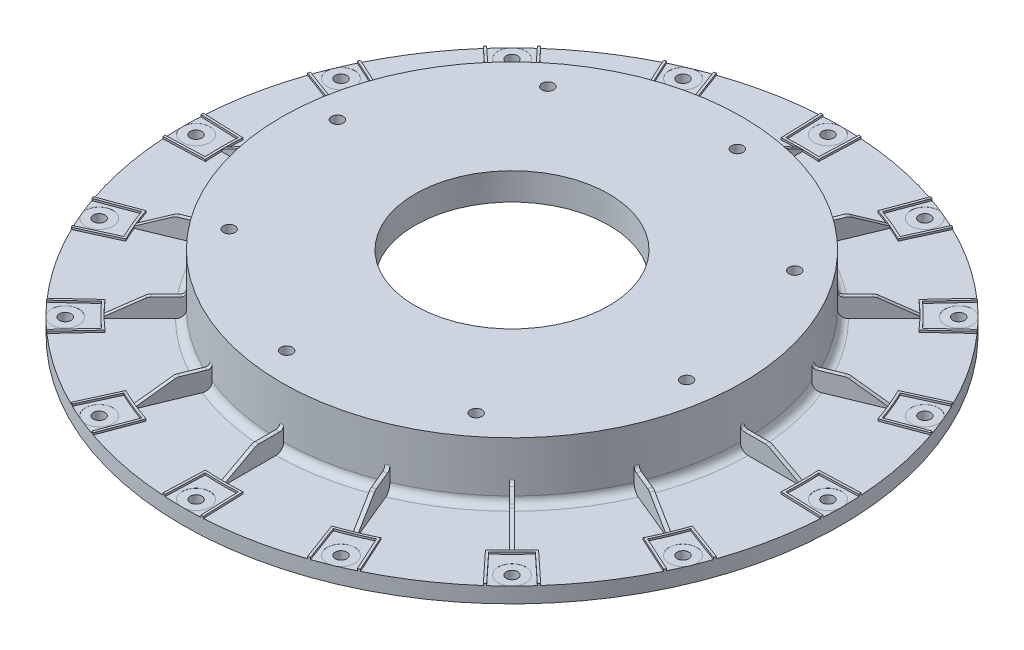
SolidWorks part; units mm, degrees
material "PF"
ref_plane "前视基准面" through (0, 0, 0) normal (0, 0, 1) x (1, 0, 0)
ref_plane "上视基准面" through (0, 0, 0) normal (0, 1, 0) x (1, 0, 0)
ref_plane "右视基准面" through (0, 0, 0) normal (1, 0, 0) x (0, 0, -1)
sketch "草图1" plane through (0, 0, 0) normal (0, 1, 0) x (1, 0, 0)
  circle A0 centre (0, 0) radius 85
  dimension "D1" = 170
extrude "凸台-拉伸1" add sketch "草图1" along normal blind 5
sketch "草图2" plane through (0, 5, 0) normal (0, 1, 0) x (1, 0, 0)
  circle A0 centre (0, 0) radius 81.5 construction
  circle A1 centre (0, 0) radius 85 construction
  circle A2 centre (-81.5, 0) radius 1.5
  dimension "D1" = 3.5
  dimension "D2" = 3
extrude "切除-拉伸1" cut sketch "草图2" against normal blind 50
pattern_circular "阵列(圆周)1" count 16 over 360 about axis through (0, 5, 0) along (0, 1, 0) of "切除-拉伸1"
sketch "草图3" plane through (0, 5, 0) normal (0, 1, 0) x (1, 0, 0)
  circle A0 centre (-75.2962, -31.1887) radius 3.55
  dimension "D1" = 7.1
extrude "切除-拉伸3" cut sketch "草图3" against normal blind 0.02
pattern_circular "阵列(圆周)2" count 16 over 360 about axis through (0, 5, 0) along (0, -1, 0) of "切除-拉伸3" reverse direction yes
sketch "草图4" plane through (0, 5, 0) normal (0, 1, 0) x (1, 0, 0)
  line L0 (-74.8787, 4.2634) -> (-84.8741, 4.625)
  line L1 (-74.8787, -4.2634) -> (-84.8741, -4.625)
  line L2 (-84.8393, 5.2242) -> (-74.2424, 4.8407)
  line L3 (-108.4611, 0) -> (191.6267, 0) construction
  line L4 (-84.8393, -5.2242) -> (-74.2424, -4.8407)
  arc A0 (-74.8787, 4.2634) -> (-74.8787, -4.2634) centre (0, 0) ccw
  arc A1 (-78.7598, 31.9671) -> (-84.9978, 0.6063) centre (0, 0) ccw construction
  arc A2 (-84.9978, -0.6063) -> (-78.7598, -31.9671) centre (0, 0) ccw construction
  arc A3 (-84.8393, 5.2242) -> (-84.8741, 4.625) centre (0, 0) ccw
  arc A4 (-74.2424, 4.8407) -> (-74.2424, -4.8407) centre (0, 0) ccw
  arc A5 (-84.8741, -4.625) -> (-84.8393, -5.2242) centre (0, 0) ccw
  point P11 (-81.5, 0)
  dimension "D1" = 10
  dimension "D5" = 0.6
  dimension "D2" = 4.5
  dimension "D3" = 4.5
  dimension "D4" = 0.6
  dimension "D6" = 0.6
extrude "凸台-拉伸2" add sketch "草图4" along normal blind 0.5
pattern_circular "阵列(圆周)3" count 16 over 360 about axis through (0, 5, 0) along (0, -1, 0) of "凸台-拉伸2" reverse direction yes
sketch "草图5" plane through (0, 0, 0) normal (0, 0, 1) x (1, 0, 0)
  line L0 (-74.4, 5.5) -> (-69.9462, 7.74)
  line L1 (-69.9462, 7.74) -> (-60.4731, 7.74)
sketch "草图6" plane through (0, 5, 0) normal (0, 1, 0) x (1, 0, 0)
  circle A0 centre (0, 0) radius 59.4
  arc A1 (-74.2424, 4.8407) -> (-74.2424, -4.8407) centre (0, 0) ccw construction
  dimension "D1" = 15
extrude "凸台-拉伸3" add sketch "草图6" along normal blind 20
sketch "草图7" plane through (0, 25, 0) normal (0, 1, 0) x (1, 0, 0)
  circle A0 centre (0, 0) radius 54.4
  circle A1 centre (0, 0) radius 59.4 construction
  dimension "D1" = 5
extrude "切除-拉伸4" cut sketch "草图7" against normal blind 50
sketch "草图8" plane through (0, 0, 0) normal (0, 0, 1) x (1, 0, 0)
  line L0 (-74.4, 5.5) -> (-66.3389, 9.8206)
  line L1 (-66.3389, 9.8206) -> (-59.4, 9.8206)
  line L2 (-59.4, 25) -> (-59.4, 5) construction
  line L5 (-56.2964, 5) -> (-49.0744, 5) construction
  line L6 (-57.9, 5) -> (-74.3212, 5)
  line L7 (-74.2424, 5) -> (-74.4, 5) construction
  line L9 (-59.4, 9.8206) -> (-57.9, 9.8206)
  line L10 (-57.9, 9.8206) -> (-57.9, 5)
  line L12 (-74.4, 5.5) -> (-74.6578, 5.5)
  line L13 (-76.3821, 5.5) -> (-66.7385, 5.5) construction
  line L14 (-74.6578, 5.5) -> (-74.6578, 5)
  line L15 (-63.6845, 5) -> (-76.3821, 5) construction
  line L16 (-74.6578, 5) -> (-74.3212, 5)
  dimension "D1" = 1.5
sketch "草图9" plane through (0, 25, 0) normal (0, 1, 0) x (1, 0, 0)
  circle A0 centre (0, 0) radius 56.4
  circle A1 centre (0, 0) radius 54.4 construction
  dimension "D1" = 2
extrude "切除-拉伸5" cut sketch "草图9" against normal blind 500
sketch "草图10" plane through (0, 25, 0) normal (0, 1, 0) x (1, 0, 0)
  circle A0 centre (0, 0) radius 58.5201
  circle A1 centre (0, 0) radius 25
  dimension "D1" = 50
extrude "凸台-拉伸5" add sketch "草图10" against normal blind 2
fillet "圆角3" radius 2 1 edges at (0, 5, 59.4)
extrude "凸台-拉伸6" add sketch "草图8" along normal mid plane 1
pattern_circular "阵列(圆周)5" count 16 over 360 about axis through (0, 5, 0) along (0, -1, 0) of "凸台-拉伸6" reverse direction yes
fillet "圆角11" radius 2 1 edges at (-66.3389, 9.8206, 0)
fillet "圆角14" radius 1 1 edges at (-59.4, 9.8206, 0)
fillet "圆角16" radius 1 1 edges at (-54.8784, 9.8206, 22.7314)
fillet "圆角17" radius 1 7 edges at (59.4, 9.8206, 0) (54.8784, 9.8206, 22.7314) (42.0021, 9.8206, 42.0021) (22.7314, 9.8206, 54.8784) (0, 9.8206, 59.4) (-22.7314, 9.8206, 54.8784) (-42.0021, 9.8206, 42.0021)
fillet "圆角18" radius 1 7 edges at (-54.8784, 9.8206, -22.7314) (-42.0021, 9.8206, -42.0021) (-22.7314, 9.8206, -54.8784) (0, 9.8206, -59.4) (22.7314, 9.8206, -54.8784) (42.0021, 9.8206, -42.0021) (54.8784, 9.8206, -22.7314)
fillet "圆角19" radius 2 8 edges at (66.3389, 9.8206, 0) (61.2892, 9.8206, 25.3868) (46.9087, 9.8206, 46.9087) (25.3868, 9.8206, 61.2892) (0, 9.8206, 66.3389) (-25.3868, 9.8206, 61.2892) (-46.9087, 9.8206, 46.9087) (-61.2892, 9.8206, 25.3868)
fillet "圆角20" radius 2 7 edges at (-61.2892, 9.8206, -25.3868) (-46.9087, 9.8206, -46.9087) (-25.3868, 9.8206, -61.2892) (0, 9.8206, -66.3389) (25.3868, 9.8206, -61.2892) (46.9087, 9.8206, -46.9087) (61.2892, 9.8206, -25.3868)
sketch "草图11" plane through (0, 25, 0) normal (0, 1, 0) x (1, 0, 0)
  circle A0 centre (51.5869, -6.5412) radius 1.5
extrude "切除-拉伸6" cut sketch "草图11" against normal blind 50
sketch "草图12" plane through (0, 23, 0) normal (0, -1, 0) x (1, 0, 0)
  circle A0 centre (51.5869, 6.5412) radius 1.5
pattern_circular "阵列(圆周)6" count 8 over 360 about axis through (0, 23, 0) along (0, 1, 0) of "切除-拉伸6" reverse direction yes
sketch "草图15" plane through (0, 23, 0) normal (0, -1, 0) x (1, 0, 0)
  circle A0 centre (0, 0) radius 56.4
extrude "凸台-拉伸7" add sketch "草图15" along normal blind 10
sketch "草图16" plane through (0, 25, 0) normal (0, 1, 0) x (1, 0, 0)
  circle A0 centre (0, 0) radius 25
extrude "切除-拉伸7" cut sketch "草图16" against normal blind 500
sketch "草图17" plane through (0, 25, 0) normal (0, 1, 0) x (1, 0, 0)
  circle A0 centre (-51.5869, 6.5412) radius 1.5
extrude "切除-拉伸8" cut sketch "草图17" against normal blind 500
pattern_circular "阵列(圆周)7" count 8 over 360 about axis through (0, 25, 0) along (0, -1, 0) of "切除-拉伸8"
sketch "草图18" plane through (0, 25, 0) normal (0, 1, 0) x (1, 0, 0)
  circle A0 centre (0, 0) radius 59.4
extrude "切除-拉伸9" cut sketch "草图18" against normal blind 5
sketch "草图19" plane through (0, 0, 0) normal (0, -1, 0) x (1, 0, 0)
  circle A0 centre (0, 0) radius 100.2176
extrude "切除-拉伸10" cut sketch "草图19" against normal blind 1
